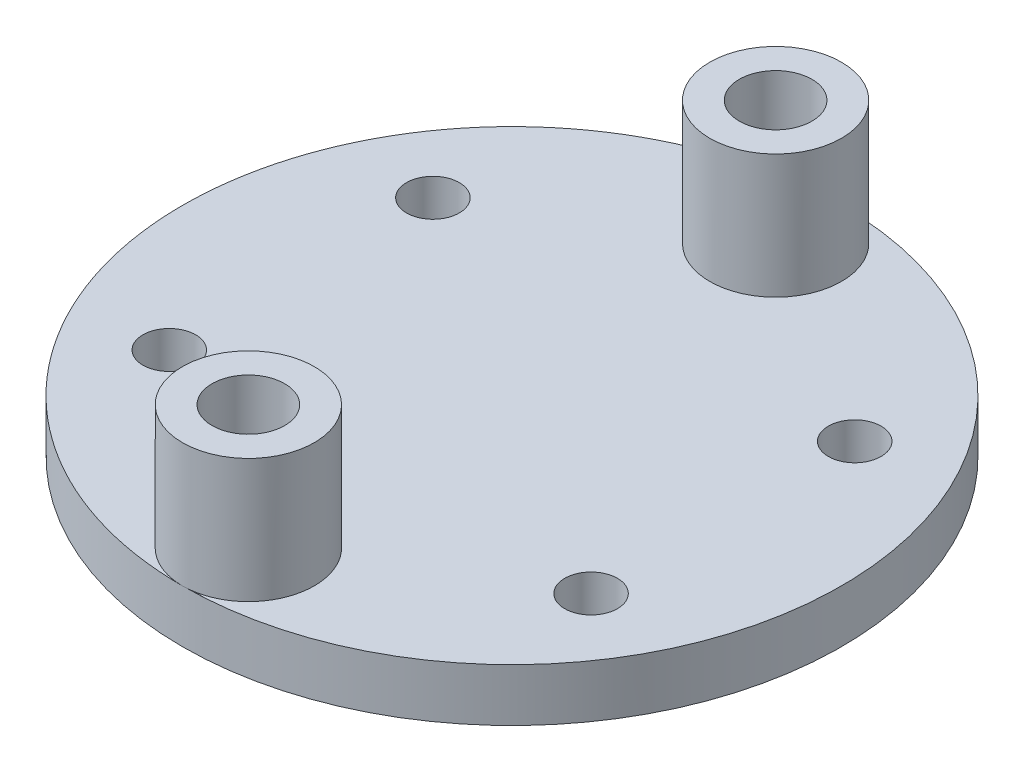
SolidWorks part; units mm, degrees
ref_plane "Front Plane" through (0, 0, 0) normal (0, 0, 1) x (1, 0, 0)
ref_plane "Top Plane" through (0, 0, 0) normal (0, 1, 0) x (1, 0, 0)
ref_plane "Right Plane" through (0, 0, 0) normal (1, 0, 0) x (0, 0, -1)
sketch "Sketch1" plane through (0, 0, 0) normal (0, 1, 0) x (1, 0, 0)
  line L0 (0, 8.89) -> (25.4, 8.89) construction
  line L5 (0, 0) -> (25.4, 0)
  line L6 (0, 0) -> (0, 17.78)
  line L7 (0, 17.78) -> (25.4, 17.78)
  line L8 (25.4, 0) -> (25.4, 17.78)
  line L9 (12.7, 17.78) -> (12.7, 0) construction
  circle A2 centre (2.54, 15.24) radius 1.27
  circle A3 centre (22.86, 15.24) radius 1.27
  circle A4 centre (22.86, 2.54) radius 1.27
  circle A5 centre (2.54, 2.54) radius 1.27
  circle A6 centre (12.7, 8.89) radius 15.875
  circle A7 centre (12.7, 21.59) radius 1.75
  circle A8 centre (12.7, -3.81) radius 1.75
  point P22 (12.7, 19.7116)
  point P23 (12.7, 19.7538)
  point P24 (12.7, 20.7875)
  point P27 (11.2937, 21.59)
  point P28 (0, 0)
  dimension "D3" = 2.54
  dimension "D6" = 31.75
  dimension "D7" = 3.5
  dimension "D1" = 17.78
  dimension "D2" = 25.4
  dimension "D4" = 20.32
  dimension "D5" = 12.7
  dimension "D8" = 12.7
extrude "Boss-Extrude1" add sketch "Sketch1" along normal blind 2.54 contours L5 L8 L7 L6 A3 A2 A4 A5 | A6 L8 L5 L6 L7 A7 A8 region at (12.7, 0, -8.89) region at (-2.726, 0, -8.89)
sketch "Sketch2" plane through (0, 2.54, 0) normal (0, 1, 0) x (1, 0, 0)
  circle A0 centre (12.7, -3.81) radius 1.75 construction
  circle A1 centre (12.7, 8.89) radius 15.875
  circle A2 centre (12.7, 8.89) radius 15.875
  circle A3 centre (12.7, 21.59) radius 1.75 construction
  circle A4 centre (12.7, -3.81) radius 1.75
  circle A5 centre (12.7, 21.59) radius 1.75
  circle A6 centre (12.7, 21.59) radius 3.175
  circle A7 centre (12.7, -3.81) radius 3.175
  circle M8 centre (12.7, 21.59) radius 1.75
  circle M9 centre (12.7, -3.81) radius 1.75
  dimension "D1" = 0
extrude "Boss-Extrude2" add sketch "Sketch2" along normal blind 5.975 contours A6 M8 | A7 M9 region at (14.8816, 2.54, -23.7716) region at (10.5184, 2.54, 1.6284)
